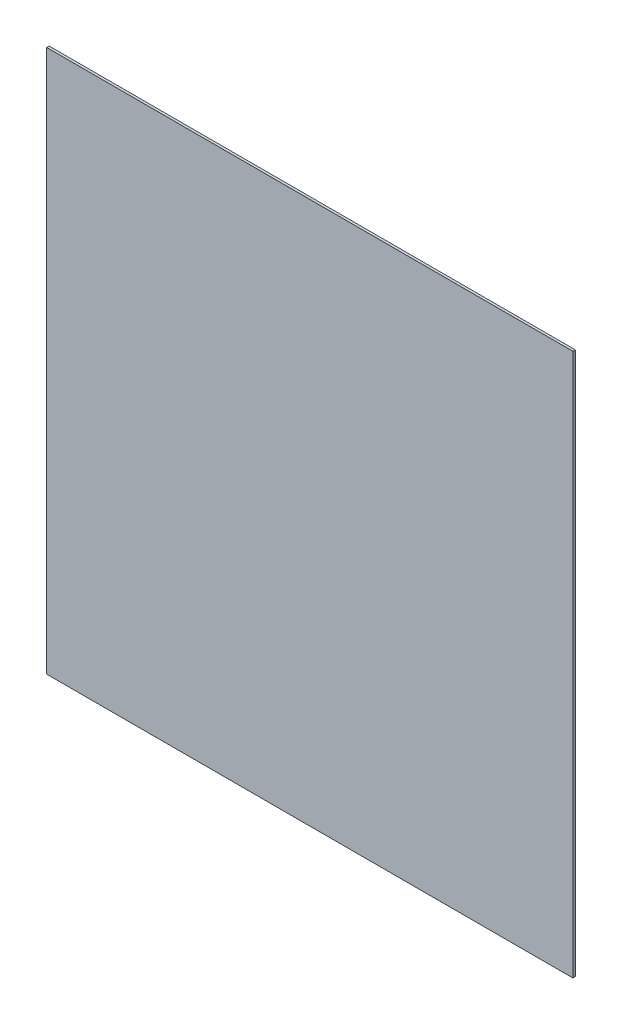
SolidWorks part; units mm, degrees
material "AISI 4130 Steel, normalized at 870C"
ref_plane "Front Plane" through (0, 0, 0) normal (0, 0, 1) x (1, 0, 0)
ref_plane "Top Plane" through (0, 0, 0) normal (0, 1, 0) x (1, 0, 0)
ref_plane "Right Plane" through (0, 0, 0) normal (1, 0, 0) x (0, 0, -1)
sketch "Sketch2" plane through (0, 0, 0) normal (0, 0, 1) x (1, 0, 0)
  line L1 (-160, 160) -> (160, 160)
  line L2 (-160, 160) -> (-160, -170)
  line L3 (-160, -170) -> (160, -170)
  line L4 (160, 160) -> (160, -170)
  dimension "D1" = 320
  dimension "D2" = 330
  dimension "D3" = 160
  dimension "D4" = 160
extrude "Boss-Extrude2" add sketch "Sketch2" along normal blind 1.5
